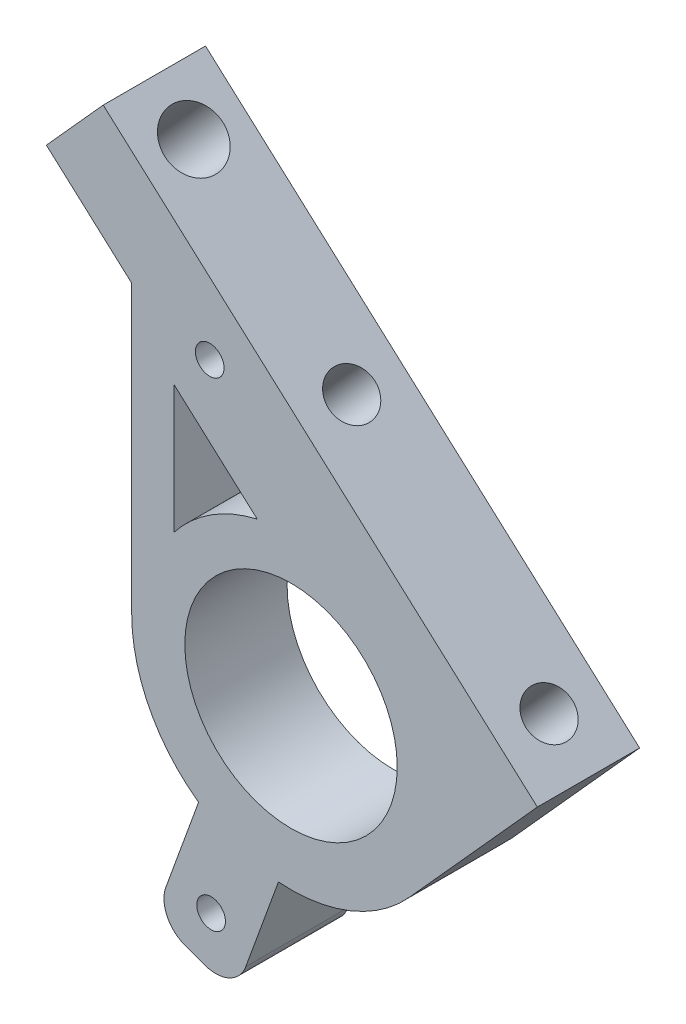
SolidWorks part; units mm, degrees
material "6061 Alloy"
ref_plane "Front Plane" through (0, 0, 0) normal (0, 0, 1) x (1, 0, 0)
ref_plane "Top Plane" through (0, 0, 0) normal (0, 1, 0) x (1, 0, 0)
ref_plane "Right Plane" through (0, 0, 0) normal (1, 0, 0) x (0, 0, -1)
sketch "Sketch1" plane through (0, 0, 0) normal (0, 0, 1) x (1, 0, 0)
  line L0 (-17.6814, 40.1418) -> (21.9261, 40.1418) construction
  line L1 (-15, 0) -> (-15, 26.9624)
  line L2 (-15, 26.9624) -> (-23.0345, 34.1967)
  line L3 (-23.0345, 34.1967) -> (-17.6814, 40.1418)
  line L4 (-17.6814, 40.1418) -> (23.1915, 3.3396)
  line L5 (23.1915, 3.3396) -> (17.8385, -2.6055)
  line L10 (17.8385, -2.6055) -> (11.1472, -10.037)
  line L11 (-15, 26.9624) -> (17.8385, -2.6055) construction
  circle A0 centre (0, 0) radius 10
  arc A1 (-15, 0) -> (11.1472, -10.037) centre (0, 0) ccw
  dimension "D3" = 20
  dimension "D4" = 5
  dimension "D1" = 42
  dimension "D2" = 8
  dimension "D7" = 55
extrude "3/8" add sketch "Sketch1" along normal blind 9.63
sketch "Sketch2" plane through (0, 0, 0) normal (0, 0, 1) x (1, 0, 0)
  line L0 (0, 0) -> (0, -7.8768) construction
  line L1 (-8.7033, -12.2169) -> (-1.1858, -14.9531)
  line L2 (-8.7033, -12.2169) -> (-12.8075, -23.4932)
  line L3 (-12.8075, -23.4932) -> (-5.29, -26.2294)
  line L4 (-1.1858, -14.9531) -> (-5.29, -26.2294)
  line L5 (-9.0488, -24.8613) -> (-4.9445, -13.585) construction
  line L6 (-10.7554, -17.8551) -> (-3.2379, -20.5912) construction
  arc A0 (-15, 0) -> (11.1472, -10.037) centre (0, 0) ccw construction
  point P360 (-6.9966, -19.2231)
  dimension "D1" = 12
  dimension "D2" = 8
  dimension "D3" = 110
extrude "Boss-Extrude2" add sketch "Sketch2" along normal up to surface (9.63 mm away) up to face at (-6.6377, 14.2697, 9.63)
sketch "Sketch3" plane through (0, 0, 9.63) normal (0, 0, 1) x (1, 0, 0)
  line L0 (0, 0) -> (-9.0488, -24.8613) construction
  line L1 (-12.8075, -23.4932) -> (-5.29, -26.2294) construction
  circle A0 centre (-7.5244, -20.6732) radius 1.35
  dimension "D2" = 2.7
  dimension "D1" = 22
extrude "M3_DRILL_or_Through" cut sketch "Sketch3" against normal up to surface (9.63 mm away) up to face at (-6.5272, 1.5509, 0)
fillet "Fillet1" radius 3 2 edges at (-5.29, -26.2294, 4.815) (-12.8075, -23.4932, 4.815)
sketch "Sketch4" plane through (12.0444, 13.3766, 0) normal (0.6691, 0.7431, 0) x (0.7431, -0.6691, 0)
  line L0 (-40, -4.815) -> (15, -4.815) construction
  line L1 (-40, -9.63) -> (-40, 0) construction
  line L2 (15, -9.63) -> (15, 0) construction
  circle A0 centre (-35, -4.815) radius 2.75
  dimension "D2" = 5.5
  dimension "D1" = 5
extrude "M5_through" cut sketch "Sketch4" against normal up to surface (8 mm away) up to face at (-19.0172, 30.5795, 4.815)
sketch "Sketch5" plane through (12.0444, 13.3766, 0) normal (0.6691, 0.7431, 0) x (0.7431, -0.6691, 0)
  line L0 (-35, -4.815) -> (10, -4.815) construction
  circle A0 centre (-15, -4.815) radius 2.2
  circle A1 centre (10, -4.815) radius 2.2
  dimension "D1" = 4.4
  dimension "D2" = 20
  dimension "D3" = 45
extrude "M5_DRILL" cut sketch "Sketch5" against normal blind 8
sketch "Sketch6" plane through (0, 0, 9.63) normal (0, 0, 1) x (1, 0, 0)
  line L0 (-11, 20.6695) -> (-11, 8.6603)
  line L1 (-11, 20.6695) -> (-3.185, 13.6329)
  line L2 (23.1915, 3.3396) -> (-17.6814, 40.1418) construction
  line L3 (-15, 26.9624) -> (-15, 0) construction
  arc A0 (-11, 8.6603) -> (-3.185, 13.6329) centre (0, 0) cw
  circle A1 centre (0, 0) radius 10 construction
  dimension "D3" = 4
  dimension "D1" = 10
  dimension "D2" = 4
extrude "Cut-Extrude4" cut sketch "Sketch6" against normal up to vertex (9.63 mm away) up to point (-17.6814, 40.1418, 0)
sketch "Sketch7" plane through (0, 0, 9.63) normal (0, 0, 1) x (1, 0, 0)
  line L0 (-11, 20.6695) -> (-4.3087, 28.101) construction
  line L1 (23.1915, 3.3396) -> (-17.6814, 40.1418) construction
  circle A0 centre (-7.6543, 24.3852) radius 1.35
  dimension "D1" = 2.7
extrude "M3_DRILL_or_Through2" cut sketch "Sketch7" against normal up to surface (9.63 mm away) up to face at (-8.5361, 14.5426, 0)
